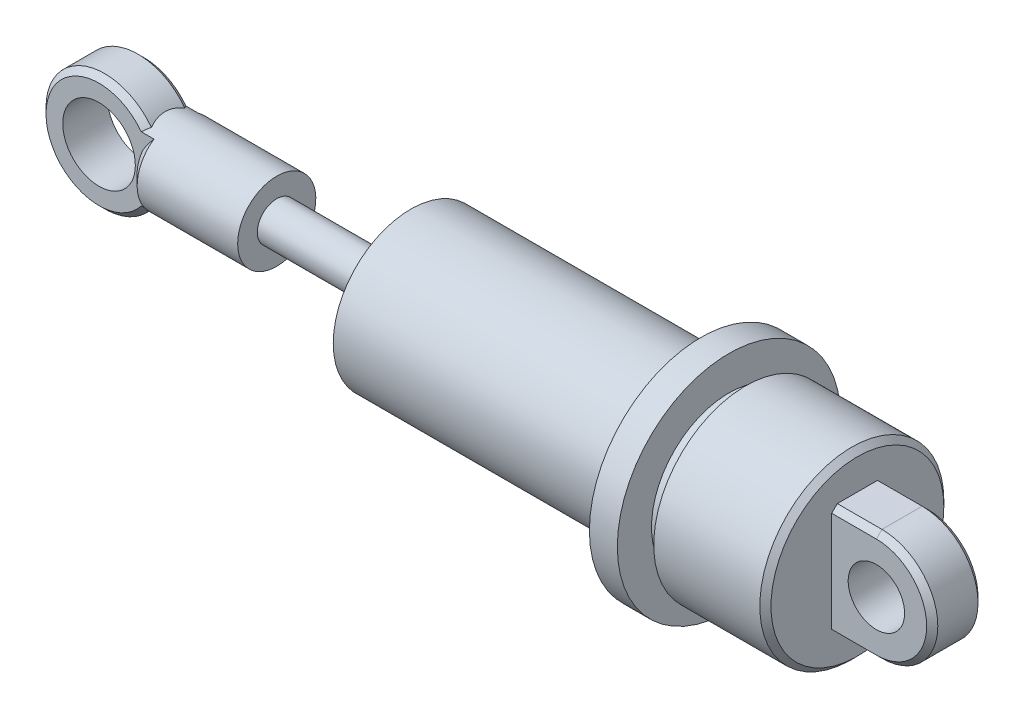
SolidWorks part; units mm, degrees
ref_plane "Piano frontale" through (0, 0, 0) normal (0, 0, 1) x (1, 0, 0)
ref_plane "Piano superiore" through (0, 0, 0) normal (0, 1, 0) x (1, 0, 0)
ref_plane "Piano destro" through (0, 0, 0) normal (1, 0, 0) x (0, 0, -1)
sketch "Schizzo2" plane through (0, 0, 0) normal (1, 0, 0) x (0, 0, -1)
  circle A0 centre (0, 0) radius 6.94
  dimension "D1" = 13.88
extrude "Estrusione-Estrusione1" add sketch "Schizzo2" along normal blind 26
sketch "Schizzo3" plane through (26, 0, 0) normal (1, 0, 0) x (0, 0, -1)
  circle A0 centre (0, 0) radius 10
  dimension "D1" = 20
extrude "Estrusione-Estrusione2" add sketch "Schizzo3" along normal blind 2.5
sketch "Schizzo4" plane through (28.5, 0, 0) normal (1, 0, 0) x (0, 0, -1)
  circle A0 centre (0, 0) radius 6.94
  circle A1 centre (0, 0) radius 6.94 construction
extrude "Estrusione-Estrusione3" add sketch "Schizzo4" along normal blind 1.5
sketch "Schizzo5" plane through (30, 0, 0) normal (1, 0, 0) x (0, 0, -1)
  circle A0 centre (0, 0) radius 8.24
  dimension "D1" = 16.48
extrude "Estrusione-Estrusione4" add sketch "Schizzo5" along normal blind 10
sketch "Schizzo6" plane through (0, 0, 0) normal (0, 0, 1) x (1, 0, 0)
  line L0 (40, 0) -> (49, 0) construction
  line L1 (40, -8.24) -> (40, 8.24) construction
  line L2 (44, -5) -> (40, -5)
  line L3 (44, 5) -> (40, 5)
  line L4 (40, -5) -> (40, 5)
  arc A0 (44, 5) -> (44, -5) centre (44, 0) cw
  circle A1 centre (44, 0) radius 2.525
  point P8 (49, 0)
  dimension "D3" = 5.05
  dimension "D1" = 10
  dimension "D2" = 9
extrude "Estrusione-Estrusione5" add sketch "Schizzo6" along normal mid plane 4.6
chamfer "Smusso1" distance 0.5 angle 45 7 edges at (40, 0, -8.24) (42, -5, 2.3) (42, 5, 2.3) (49, 0, 2.3) (42, -5, -2.3) (42, 5, -2.3) (49, 0, -2.3)
sketch "Schizzo7" plane through (0, 0, 0) normal (-1, 0, 0) x (0, 0, 1)
  circle A0 centre (0, 0) radius 1.745
  dimension "D1" = 3.49
sketch "Schizzo10" plane through (0, 0, 0) normal (0, 1, 0) x (1, 0, 0)
  line L0 (0, 0) -> (-12, 0)
  line L1 (0, 1.745) -> (0, -1.745) construction
  dimension "D1" = 12
sweep "Sweep1" add profiles "Schizzo7" path "Schizzo10"
sketch "Schizzo8" plane through (-12, 0, 0) normal (-1, 0, 0) x (0, 0, 1)
  circle A0 centre (0, 0) radius 3.5
  dimension "D1" = 7
extrude "Estrusione-Estrusione7" add sketch "Schizzo8" along normal blind 10
sketch "Schizzo9" plane through (0, 0, 0) normal (0, 0, 1) x (1, 0, 0)
  line L0 (-22, 0) -> (-25.9131, 0) construction
  line L1 (-22, 3.5) -> (-22, -3.5) construction
  circle A0 centre (-25.9131, 0) radius 5.25
  circle A1 centre (-25.9131, 0) radius 3.25
  dimension "D1" = 10.5
  dimension "D2" = 6.5
extrude "Estrusione-Estrusione8" add sketch "Schizzo9" along normal mid plane 4
chamfer "Smusso2" distance 1 angle 45 2 edges at (-22, 0, -3.5) (-22, 0, 3.5)
chamfer "Smusso3" distance 0.5 angle 45 2 edges at (-31.1631, 0, 2) (-31.1631, 0, -2)
